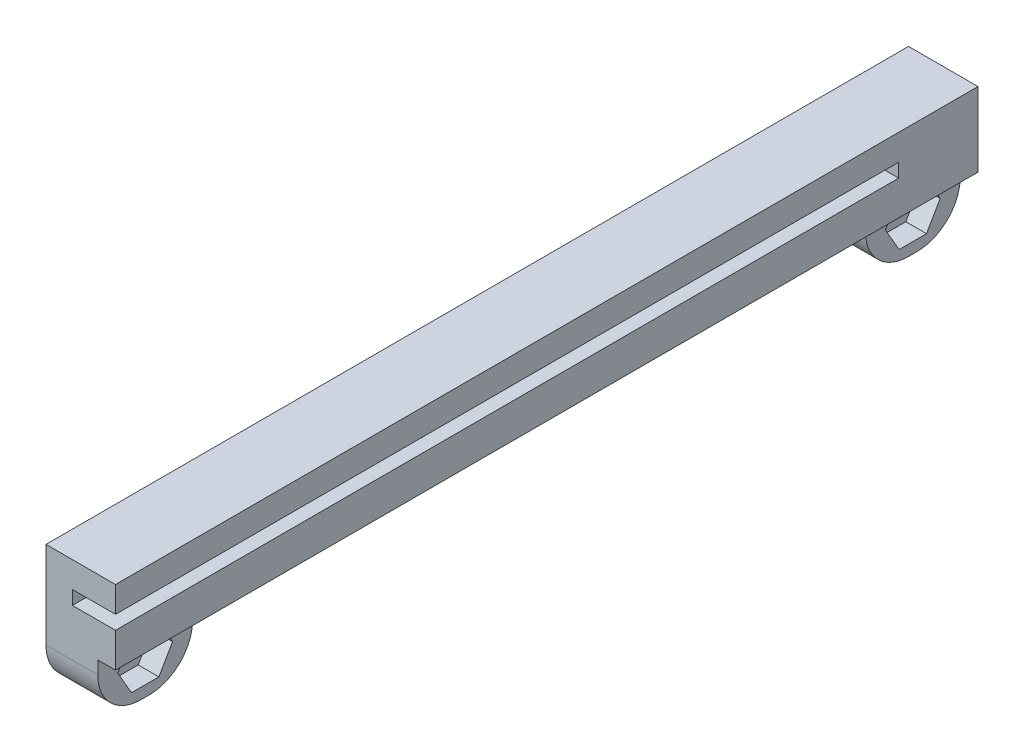
SolidWorks part; units mm, degrees
ref_plane "Front Plane" through (0, 0, 0) normal (0, 0, 1) x (1, 0, 0)
ref_plane "Top Plane" through (0, 0, 0) normal (0, 1, 0) x (1, 0, 0)
ref_plane "Right Plane" through (0, 0, 0) normal (1, 0, 0) x (0, 0, -1)
sketch "Sketch1" plane through (0, 0, 0) normal (0, 1, 0) x (1, 0, 0)
  line L1 (-3.5288, -50) -> (3.5288, -50)
  line L2 (-3.5288, -50) -> (-3.5288, 50)
  line L3 (-3.5288, 50) -> (3.5288, 50)
  line L4 (3.5288, -50) -> (3.5288, 50)
  line L5 (-3.5288, -50) -> (3.5288, 50) construction
  line L6 (-3.5288, 50) -> (3.5288, -50) construction
  point P0 (0, 0)
  dimension "D1" = 100
  dimension "D2" = 7.0575
extrude "Boss-Extrude2" add sketch "Sketch1" along normal blind 7.6
sketch "Sketch4" plane through (0, 7.6, 0) normal (0, 1, 0) x (1, 0, 0)
  line L0 (3.5288, -50) -> (3.5288, 50) construction
  line L1 (3.5288, 40.805) -> (-1.4713, 40.805)
  line L2 (3.5288, 40.805) -> (3.5288, -50)
  line L3 (3.5288, -50) -> (-1.4713, -50)
  line L4 (-1.4713, 40.805) -> (-1.4713, -50)
  line L5 (-3.5288, -50) -> (3.5288, -50) construction
  line L7 (-3.5288, 50) -> (-3.5288, -50) construction
  dimension "D1" = 90.805
  dimension "D2" = 2.0575
extrude "Cut-Extrude1" cut sketch "Sketch4" against normal blind 4.6
sketch "Sketch6" plane through (0, 7.6, 0) normal (0, 1, 0) x (1, 0, 0)
  line L1 (3.5288, 40.805) -> (-1.4713, 40.805)
  line L2 (3.5288, 40.805) -> (3.5288, -50)
  line L3 (3.5288, -50) -> (-1.4713, -50)
  line L4 (-1.4713, 40.805) -> (-1.4713, -50)
extrude "Boss-Extrude3" add sketch "Sketch6" against normal blind 3
sketch "Sketch8" plane through (0, 0, 0) normal (0, -1, 0) x (1, 0, 0)
  line L1 (-3.5288, 50) -> (3.5288, 50)
  line L2 (-3.5288, 50) -> (-3.5288, -50)
  line L3 (-3.5288, -50) -> (3.5288, -50)
  line L4 (3.5288, 50) -> (3.5288, -50)
extrude "Boss-Extrude4" add sketch "Sketch8" along normal blind 1
sketch "Sketch9" plane through (0, -1, 0) normal (0, -1, 0) x (1, 0, 0)
  line L1 (-3.5288, 50) -> (1.4712, 50)
  line L2 (-3.5288, 50) -> (-3.5288, 39)
  line L3 (-3.5288, 39) -> (1.4712, 39)
  line L4 (1.4712, 50) -> (1.4712, 39)
  line L5 (-3.5288, -50) -> (1.4712, -50)
  line L6 (-3.5288, -50) -> (-3.5288, -39)
  line L7 (-3.5288, -39) -> (1.4712, -39)
  line L8 (1.4712, -50) -> (1.4712, -39)
  point P10 (1.4712, -44.5)
  dimension "D1" = 11
  dimension "D2" = 11
  dimension "D3" = 5
  dimension "D4" = 5
extrude "Boss-Extrude5" add sketch "Sketch9" along normal blind 6.5 contours L2 L1 L4 L3 | L6 L5 L8 L7
sketch "Sketch10" plane through (1.4713, 0, 0) normal (1, 0, 0) x (0, 0, -1)
  line L0 (-50, -7.5) -> (-50, -1) construction
  line L1 (-46.0877, -0.75) -> (-47.6754, -3.5)
  line L2 (-47.6754, -3.5) -> (-46.0877, -6.25)
  line L3 (-46.0877, -6.25) -> (-42.9123, -6.25)
  line L4 (-42.9123, -6.25) -> (-41.3246, -3.5)
  line L5 (-41.3246, -3.5) -> (-42.9123, -0.75)
  line L6 (-42.9123, -0.75) -> (-46.0877, -0.75)
  line L7 (-50, -7.5) -> (-39, -7.5) construction
  line L8 (39, -7.5) -> (39, -1) construction
  line L9 (47.6754, -3.5) -> (46.0877, -0.75)
  line L10 (46.0877, -0.75) -> (42.9123, -0.75)
  line L11 (42.9123, -0.75) -> (41.3246, -3.5)
  line L12 (41.3246, -3.5) -> (42.9123, -6.25)
  line L13 (42.9123, -6.25) -> (46.0877, -6.25)
  line L14 (46.0877, -6.25) -> (47.6754, -3.5)
  line L15 (50, -7.5) -> (39, -7.5) construction
  circle A0 centre (-44.5, -3.5) radius 2.75 construction
  circle A1 centre (44.5, -3.5) radius 2.75 construction
  dimension "D1" = 5.5
  dimension "D2" = 5.5
  dimension "D3" = 1.25
  dimension "D4" = 5.5
  dimension "D5" = 1.25
  dimension "D6" = 5.5
extrude "Cut-Extrude2" cut sketch "Sketch10" against normal blind 2.4
sketch "Sketch11" plane through (-0.9287, 0, 0) normal (1, 0, 0) x (0, 0, -1)
  line L2 (-50, -7.5) -> (-39, -7.5) construction
  line L3 (-50, -7.5) -> (-50, -1) construction
  line L4 (39, -7.5) -> (39, -1) construction
  line L5 (50, -7.5) -> (39, -7.5) construction
  circle A0 centre (-44.5, -3.5) radius 1.5
  circle A1 centre (44.5, -3.5) radius 1.5
  dimension "D3" = 3
  dimension "D4" = 3
  dimension "D1" = 4
  dimension "D2" = 5.5
  dimension "D5" = 5.5
  dimension "D6" = 4
extrude "Cut-Extrude3" cut sketch "Sketch11" against normal through all contours A0 | A1
fillet "Fillet2" radius 5 4 edges at (-1.0288, -7.5, -50) (-1.0288, -7.5, -39) (-1.0288, -7.5, 39) (-1.0288, -7.5, 50)
sketch "Sketch13" plane through (-3.5288, 0, 0) normal (-1, 0, 0) x (0, 0, 1)
  line L0 (-45, -7.5) -> (-44, -7.5) construction
  line L1 (-39, -2.5) -> (-39, -1) construction
  line L2 (39, -1) -> (-39, -1) construction
  line L3 (39, -2.5) -> (39, -1) construction
  line L4 (45, -7.5) -> (44, -7.5) construction
  line L5 (50, 7.6) -> (50, -2.5) construction
  line L6 (-50, 7.6) -> (50, 7.6) construction
  line L7 (-50, 7.6) -> (-50, -2.5) construction
  line L8 (-45, -7.5) -> (-44, -7.5)
  line L9 (-39, -2.5) -> (-39, -1)
  line L10 (39, -1) -> (-39, -1)
  line L11 (39, -2.5) -> (39, -1)
  line L12 (45, -7.5) -> (44, -7.5)
  line L13 (50, 7.6) -> (50, -2.5)
  line L14 (-50, 7.6) -> (50, 7.6)
  line L15 (-50, 7.6) -> (-50, -2.5)
  circle A0 centre (-44.5, -3.5) radius 1.5 construction
  arc A1 (-50, -2.5) -> (-45, -7.5) centre (-45, -2.5) ccw construction
  arc A2 (-44, -7.5) -> (-39, -2.5) centre (-44, -2.5) ccw construction
  arc A3 (39, -2.5) -> (44, -7.5) centre (44, -2.5) ccw construction
  circle A4 centre (44.5, -3.5) radius 1.5 construction
  arc A5 (45, -7.5) -> (50, -2.5) centre (45, -2.5) ccw construction
  circle A6 centre (-44.5, -3.5) radius 1.5
  arc A7 (-50, -2.5) -> (-45, -7.5) centre (-45, -2.5) ccw
  arc A8 (-44, -7.5) -> (-39, -2.5) centre (-44, -2.5) ccw
  arc A9 (39, -2.5) -> (44, -7.5) centre (44, -2.5) ccw
  circle A10 centre (44.5, -3.5) radius 1.5
  arc A11 (45, -7.5) -> (50, -2.5) centre (45, -2.5) ccw
extrude "Boss-Extrude6" add sketch "Sketch13" along normal blind 1
mirror "Mirror2" [suppressed] of bodies 109
delete or keep bodies "Body-Delete/Keep 1" [suppressed] type delete bodies bodies 109
